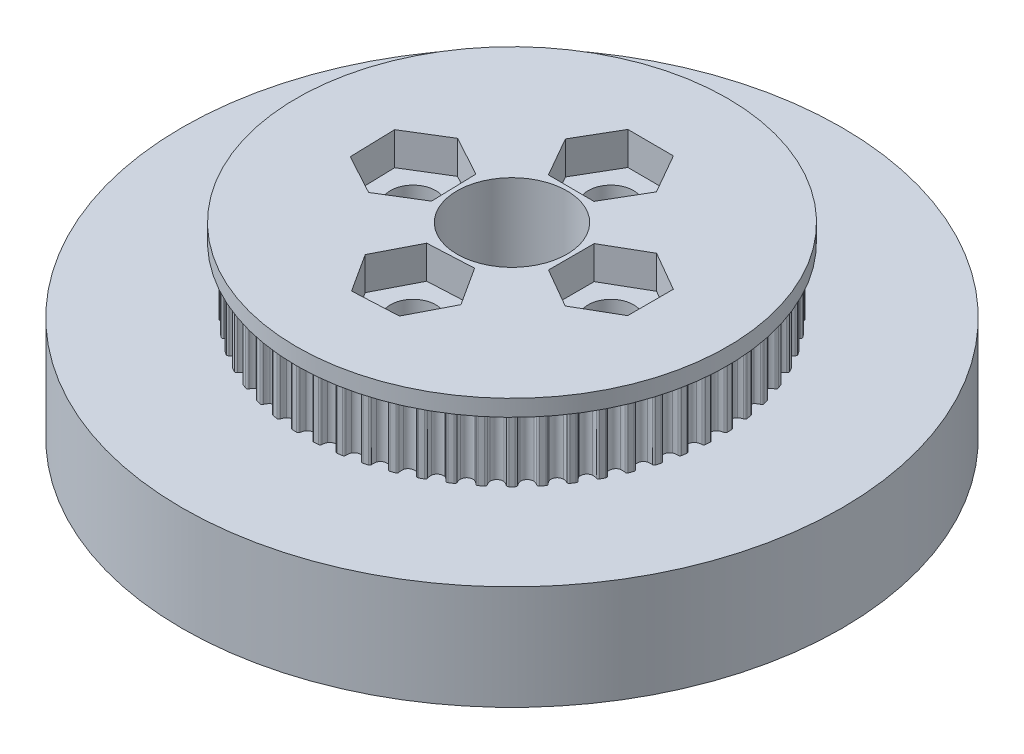
SolidWorks part; units mm, degrees
ref_plane "Front Plane" through (0, 0, 0) normal (0, 0, 1) x (1, 0, 0)
ref_plane "Top Plane" through (0, 0, 0) normal (0, 1, 0) x (1, 0, 0)
ref_plane "Right Plane" through (0, 0, 0) normal (1, 0, 0) x (0, 0, -1)
sketch "Sketch1" plane through (0, 0, 0) normal (0, 1, 0) x (1, 0, 0)
  circle A0 centre (0, 0) radius 18.8446
  dimension "D1" = 37.6892
extrude "Boss-Extrude1" add sketch "Sketch1" along normal blind 6
sketch "Sketch2" plane through (0, 6, 0) normal (0, 1, 0) x (1, 0, 0)
  line L0 (0, 0) -> (0, 18.8446) construction
  line L1 (0, 18.8446) -> (-0.4, 18.8446) construction
  line L2 (0, 18.8446) -> (0.4, 18.8446) construction
  circle A0 centre (0, 0) radius 18.8446
  circle A1 centre (0, 0) radius 18.6396 construction
  circle A2 centre (0, 0) radius 18.0846 construction
  arc A4 (-0.6199, 18.8344) -> (-0.4536, 18.2862) centre (0.4, 18.8446) ccw
  arc A5 (-0.4536, 18.2862) -> (0.4536, 18.2862) centre (0, 18.6396) ccw
  arc A6 (0.4536, 18.2862) -> (0.6199, 18.8344) centre (-0.4, 18.8446) ccw
  dimension "D1" = 37.6892
  dimension "D2" = 36.1692
  dimension "D3" = 37.2792
  dimension "D7" = 2.04
  dimension "D8" = 1.15
  dimension "D4" = 0.4
  dimension "D5" = 0.4
extrude "Cut-Extrude1" cut sketch "Sketch2" against normal blind 10 contours A5 A6 A0 A4 region at (0, 6, -18.5075)
fillet "Fillet1" radius 0.17 2 edges at (0.6199, 3, -18.8344) (-0.6199, 3, -18.8344)
ref_axis "Axis2" through (0, 6, 0) along (0, -1, 0)
pattern_circular "CirPattern2" count 60 over 360 about axis through (0, 6, 0) along (0, -1, 0) of "Cut-Extrude1", "Fillet1"
sketch "Sketch3" plane through (0, 6, 0) normal (0, 1, 0) x (1, 0, 0)
  circle A0 centre (0, 0) radius 19.5946
  dimension "D1" = 39.1892
extrude "Boss-Extrude2" add sketch "Sketch3" along normal blind 1.5
sketch "Sketch4" plane through (0, 0, 0) normal (0, -1, 0) x (1, 0, 0)
  circle A0 centre (0, 0) radius 30
  dimension "D1" = 60
extrude "Boss-Extrude3" add sketch "Sketch4" along normal blind 9.5
sketch "Sketch5" plane through (0, -9.5, 0) normal (0, -1, 0) x (1, 0, 0)
  circle A0 centre (0, 0) radius 24.5
  dimension "D1" = 49
extrude "Cut-Extrude2" cut sketch "Sketch5" against normal blind 4
sketch "Sketch6" plane through (0, -5.5, 0) normal (0, -1, 0) x (1, 0, 0)
  circle A0 centre (0, 0) radius 17
  dimension "D1" = 34
extrude "Boss-Extrude4" add sketch "Sketch6" along normal blind 2
sketch "Sketch7" plane through (0, -7.5, 0) normal (0, -1, 0) x (1, 0, 0)
  circle A0 centre (0, 0) radius 12.5
  dimension "D1" = 25
extrude "Boss-Extrude5" add sketch "Sketch7" along normal blind 11.5
sketch "Sketch8" plane through (0, -19, 0) normal (0, -1, 0) x (1, 0, 0)
  circle A0 centre (0, 0) radius 9 construction
  circle A1 centre (0, 9) radius 2.05
  circle A2 centre (9, 0) radius 2.05
  circle A3 centre (0, -9) radius 2.05
  circle A4 centre (-9, 0) radius 2.05
  dimension "D1" = 4.1
  dimension "D2" = 18
extrude "Cut-Extrude3" cut sketch "Sketch8" against normal through all
sketch "Sketch9" plane through (0, 7.5, 0) normal (0, 1, 0) x (1, 0, 0)
  line L1 (-4.1518, -9.2059) -> (-1.8976, -12.6986)
  line L2 (-1.8976, -12.6986) -> (2.2543, -12.4926)
  line L3 (2.2543, -12.4926) -> (4.1518, -8.7941)
  line L4 (4.1518, -8.7941) -> (1.8976, -5.3014)
  line L5 (1.8976, -5.3014) -> (-2.2543, -5.5074)
  line L6 (-2.2543, -5.5074) -> (-4.1518, -9.2059)
  line L13 (-9.1114, 4.1554) -> (-12.6544, 1.9812)
  line L14 (-12.6544, 1.9812) -> (-12.543, -2.1742)
  line L15 (-12.543, -2.1742) -> (-8.8886, -4.1554)
  line L16 (-8.8886, -4.1554) -> (-5.3456, -1.9812)
  line L17 (-5.3456, -1.9812) -> (-5.457, 2.1742)
  line L18 (-5.457, 2.1742) -> (-9.1114, 4.1554)
  line L19 (-2.0634, 12.6087) -> (-4.1569, 9.0174)
  line L20 (-4.1569, 9.0174) -> (-2.0935, 5.4087)
  line L21 (-2.0935, 5.4087) -> (2.0634, 5.3913)
  line L22 (2.0634, 5.3913) -> (4.1569, 8.9826)
  line L23 (4.1569, 8.9826) -> (2.0935, 12.5913)
  line L24 (2.0935, 12.5913) -> (-2.0634, 12.6087)
  line L25 (9, 4.1569) -> (5.4, 2.0785)
  line L26 (5.4, 2.0785) -> (5.4, -2.0785)
  line L27 (5.4, -2.0785) -> (9, -4.1569)
  line L28 (9, -4.1569) -> (12.6, -2.0785)
  line L29 (12.6, -2.0785) -> (12.6, 2.0785)
  line L30 (12.6, 2.0785) -> (9, 4.1569)
  circle A0 centre (0, -9) radius 3.6 construction
  circle A1 centre (-9, 0) radius 3.6 construction
  circle A2 centre (0, 9) radius 3.6 construction
  circle A3 centre (9, 0) radius 3.6 construction
  point P18 (-5.457, -2.1742)
  point P29 (-1.8976, -5.9407)
  point P38 (-2.0634, 5.3913)
  point P39 (9, 4.1554)
  dimension "D1" = 7.2
  dimension "D2" = 7.2
  dimension "D3" = 7.2
  dimension "D4" = 7.2
extrude "Cut-Extrude4" cut sketch "Sketch9" against normal blind 3
sketch "Sketch10" plane through (0, 7.5, 0) normal (0, 1, 0) x (1, 0, 0)
  circle A0 centre (0, 0) radius 5
  dimension "D1" = 10
extrude "Cut-Extrude5" cut sketch "Sketch10" against normal through all
equation "\"GD\"= 0.76mm"
equation "\"SBD\"= 2mm"
equation "\"NT\"= 60"
equation "\"PD\"= ( \"SBD\" * \"NT\" ) / 3.14159"
equation "\"U\"= 0.254mm"
equation "\"OD\"= \"PD\" - ( 2 * \"U\" )"
equation "\"RD\"= \"OD\" - ( 2 * \"GD\" )"
equation "\"R3\"= 0.555mm"
equation "\"R2\"= 1mm"
equation "\"R1\"= 0.15mm"
equation "\"DT\"= 0.02mm"
equation "\"b\"= 0.4mm"
equation "\"D1@Sketch1\"= \"OD\""
equation "\"D1@Sketch2\"= \"OD\""
equation "\"D3@Sketch2\"= \"RD\" + \"R3\" * 2"
equation "\"D2@Sketch2\"= \"RD\""
equation "\"D4@Sketch2\"= \"b\""
equation "\"D5@Sketch2\"= \"b\""
equation "\"D7@Sketch2\"= ( \"R2\" + \"DT\" ) * 2"
equation "\"D8@Sketch2\"= ( \"R3\" + \"DT\" ) * 2"
equation "\"D1@Fillet1\"=\"R1\"+\"DT\""
equation "\"D1@CirPattern2\"=\"NT\""
equation "\"D1@Sketch3\"=\"OD\"+1.5mm"
